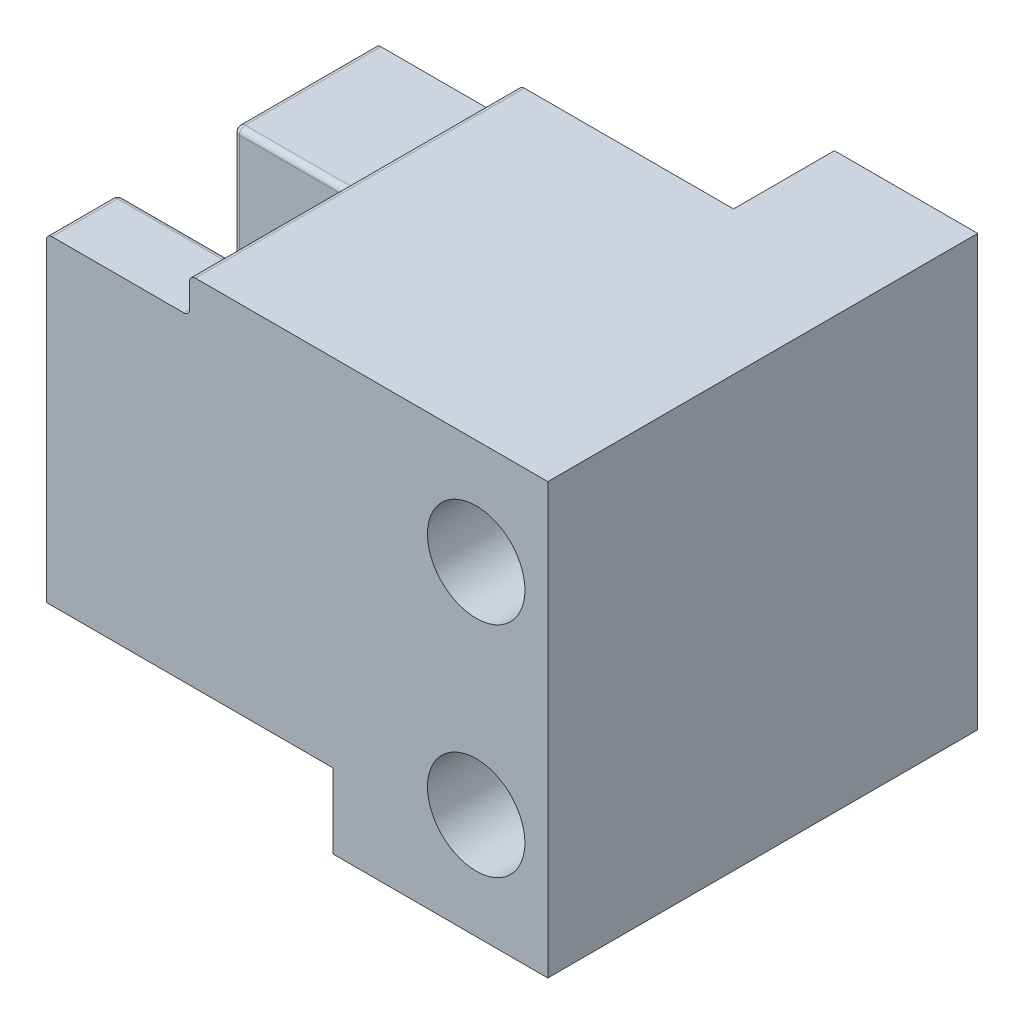
SolidWorks part; units mm, degrees
material "ABS"
ref_plane "Front Plane" through (0, 0, 0) normal (0, 0, 1) x (1, 0, 0)
ref_plane "Top Plane" through (0, 0, 0) normal (0, 1, 0) x (1, 0, 0)
ref_plane "Right Plane" through (0, 0, 0) normal (1, 0, 0) x (0, 0, -1)
sketch "Sketch1" plane through (0, 0, 0) normal (0, 0, 1) x (1, 0, 0)
  line L0 (3.175, 14.3764) -> (3.175, 4.6736) construction
  line L1 (0, 0) -> (6.35, 0)
  line L2 (0, 0) -> (0, 19.05)
  line L3 (0, 19.05) -> (6.35, 19.05)
  line L4 (6.35, 0) -> (6.35, 19.05)
  circle A0 centre (3.175, 14.3764) radius 2.159
  circle A1 centre (3.175, 4.6736) radius 2.159
  point P9 (3.175, 9.525)
  point P10 (0, 9.525)
  point P13 (3.175, 0)
  dimension "D4" = 4.318
  dimension "D1" = 19.05
  dimension "D2" = 6.35
  dimension "D3" = 9.7028
extrude "Boss-Extrude1" add sketch "Sketch1" along normal blind 19.05
sketch "Sketch2" plane through (0, 0, 0) normal (-1, 0, 0) x (0, 0, 1)
  line L0 (19.05, 19.05) -> (0, 19.05) construction
  line L1 (4.4704, 0) -> (19.05, 0)
  line L2 (4.4704, 0) -> (4.4704, 19.05)
  line L3 (4.4704, 19.05) -> (19.05, 19.05)
  line L4 (19.05, 0) -> (19.05, 19.05)
  line L6 (19.05, 0) -> (0, 0) construction
  line L7 (0, 19.05) -> (0, 0) construction
  dimension "D1" = 4.4704
extrude "Boss-Extrude2" add sketch "Sketch2" along normal blind 19.05
ref_plane "Plane1" through (0, 0, 13.316) normal (0, 0, -1) x (-1, 0, 0)
sketch "Sketch3" plane through (0, 0, 13.316) normal (0, 0, -1) x (-1, 0, 0)
  line L0 (19.05, 19.05) -> (19.05, 0) construction
  circle A0 centre (31.4198, 9.525) radius 22.352
  circle A1 centre (-3.175, 4.6736) radius 2.159 construction
  point P7 (19.05, 9.525)
  dimension "D1" = 44.704
  dimension "D2" = 34.5948
extrude "Cut-Extrude1" cut sketch "Sketch3" against normal mid plane 5.1435
sketch "Sketch4" plane through (0, 0, 19.05) normal (0, 0, -1) x (-1, 0, 0)
  line L0 (0, 0) -> (-6.35, 0) construction
  line L1 (19.05, 19.05) -> (15.875, 19.05)
  line L2 (19.05, 19.05) -> (19.05, 0)
  line L3 (19.05, 0) -> (15.875, 0)
  line L4 (15.875, 19.05) -> (15.875, 0)
  dimension "D1" = 3.175
extrude "Cut-Extrude2" cut sketch "Sketch4" along normal up to surface (19.05 mm away) up to face at (5.334, 14.3764, 0)
sketch "Sketch6" plane through (0, 0, 19.05) normal (0, 0, 1) x (1, 0, 0)
  line L0 (-15.875, 9.525) -> (6.35, 9.525) construction
  line L1 (-15.875, 0) -> (-9.525, 0)
  line L2 (-15.875, 0) -> (-15.875, 1.5875)
  line L3 (-15.875, 1.5875) -> (-9.525, 1.5875)
  line L4 (-9.525, 0) -> (-9.525, 1.5875)
  line L5 (-15.875, 19.05) -> (-15.875, 0) construction
  line L6 (6.35, 0) -> (6.35, 19.05) construction
  line L7 (-9.525, 19.05) -> (-9.525, 17.4625)
  line L8 (-15.875, 17.4625) -> (-9.525, 17.4625)
  line L9 (-15.875, 19.05) -> (-15.875, 17.4625)
  line L10 (-15.875, 19.05) -> (-9.525, 19.05)
  dimension "D1" = 1.5875
  dimension "D2" = 6.35
extrude "Cut-Extrude3" cut sketch "Sketch6" against normal up to next
fillet "Fillet2" radius 0.254 14 edges at (-13.1998, 17.4625, 15.8877) (-13.1998, 1.5875, 15.8877) (-15.875, 9.525, 15.8877) (-15.875, 1.5875, 17.4688) (-15.875, 17.4625, 17.4688) (-9.525, 1.5875, 11.7602) (-9.525, 17.4625, 11.7602) (-9.525, 19.05, 11.7602) (-9.525, 0, 11.7602) (-13.1998, 1.5875, 10.7442) (-15.875, 1.5875, 7.6073) (-15.875, 17.4625, 7.6073) (-13.1998, 17.4625, 10.7442) (-15.875, 9.525, 10.7442)
fillet "Fillet3" radius 6.35 2 edges at (-10.5246, 1.5875, 13.3159) (-10.5246, 17.4625, 13.3159)
sketch "Sketch7" plane through (0, 0, 19.05) normal (0, 0, 1) x (1, 0, 0)
  line L1 (-3.175, 3.302) -> (-15.875, 3.302)
  line L2 (-3.175, 3.302) -> (-3.175, 0)
  line L3 (-3.175, 0) -> (-15.875, 0)
  line L4 (-15.875, 3.302) -> (-15.875, 0)
  line L5 (-15.875, 17.2085) -> (-15.875, 1.8415) construction
  line L6 (-9.271, 0) -> (6.35, 0) construction
  dimension "D1" = 3.302
  dimension "D2" = 12.7
extrude "Cut-Extrude4" cut sketch "Sketch7" against normal up to next
